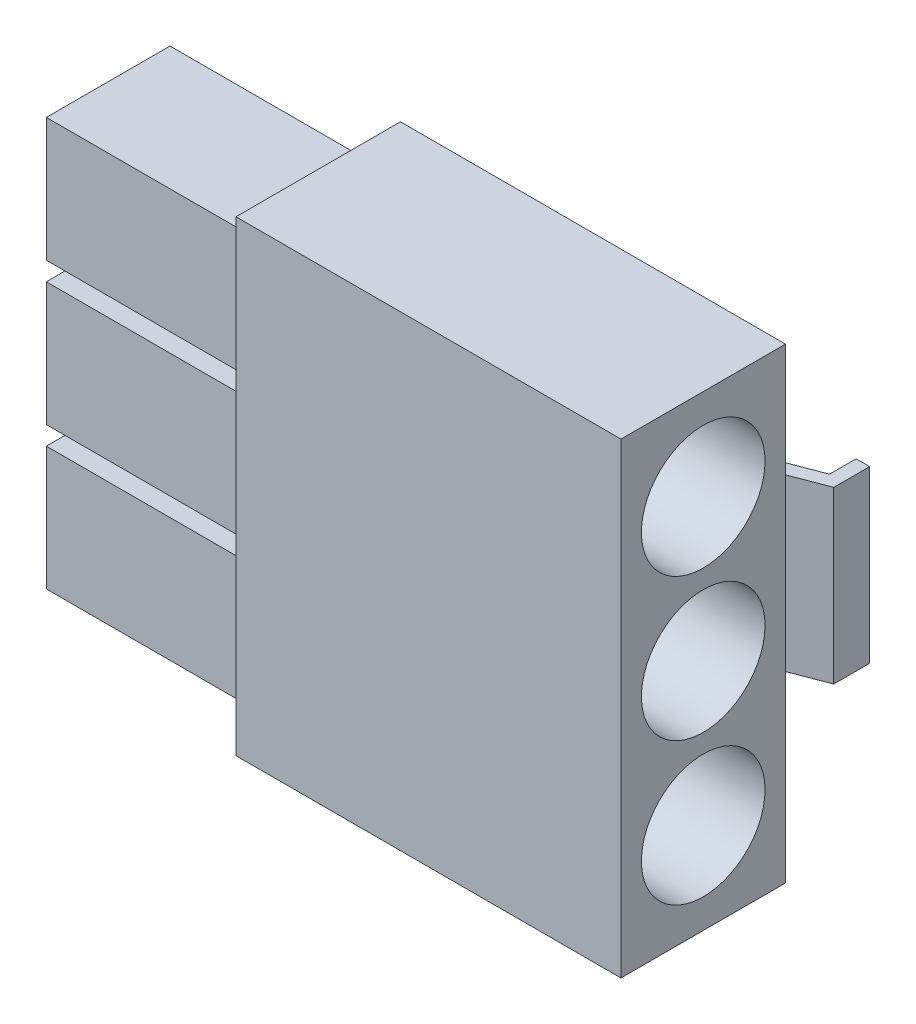
SolidWorks part; units mm, degrees
ref_plane "前视基准面" through (0, 0, 0) normal (0, 0, 1) x (1, 0, 0)
ref_plane "上视基准面" through (0, 0, 0) normal (0, 1, 0) x (1, 0, 0)
ref_plane "右视基准面" through (0, 0, 0) normal (1, 0, 0) x (0, 0, -1)
sketch "草图1" plane through (0, 0, 0) normal (0, 0, 1) x (1, 0, 0)
  line L1 (-8.25, -10) -> (8.25, -10)
  line L2 (-8.25, -10) -> (-8.25, 10)
  line L3 (-8.25, 10) -> (8.25, 10)
  line L4 (8.25, -10) -> (8.25, 10)
  line L5 (-8.25, -10) -> (8.25, 10) construction
  line L6 (-8.25, 10) -> (8.25, -10) construction
  point P0 (0, 0)
  dimension "D1" = 16.5
  dimension "D2" = 20
extrude "凸台-拉伸1" add sketch "草图1" along normal blind 7.05
sketch "草图2" plane through (-8.25, 0, 0) normal (-1, 0, 0) x (0, 0, 1)
  line L0 (0, -10) -> (7.05, 10) construction
  line L1 (0, 10) -> (7.05, -10) construction
  line L2 (0.875, 8.75) -> (6.175, 8.75)
  line L3 (0.875, -2.65) -> (6.175, -2.65)
  line L4 (0.875, -2.65) -> (0.875, 2.65)
  line L5 (0.875, 2.65) -> (6.175, 2.65)
  line L6 (6.175, -2.65) -> (6.175, 2.65)
  line L7 (0.875, -2.65) -> (6.175, 2.65) construction
  line L8 (0.875, 2.65) -> (6.175, -2.65) construction
  line L9 (6.175, 3.45) -> (6.175, 8.75)
  line L10 (0.875, 3.45) -> (6.175, 3.45)
  line L11 (0.875, 3.45) -> (0.875, 8.75)
  line L12 (0.875, -8.75) -> (6.175, -8.75)
  line L13 (0.875, -3.45) -> (6.175, -3.45)
  line L14 (0.875, -8.75) -> (0.875, -3.45)
  line L15 (6.175, -8.75) -> (6.175, -3.45)
  point P8 (3.525, 0)
  dimension "D1" = 5.3
  dimension "D2" = 5.3
  dimension "D3" = 0.8
  dimension "D4" = 0.8
extrude "凸台-拉伸2" add sketch "草图2" along normal blind 9
sketch "草图3" plane through (8.25, 0, 0) normal (1, 0, 0) x (0, 0, -1)
  line L0 (-7.05, -10) -> (0, 10) construction
  line L1 (0, -10) -> (-7.05, 10) construction
  circle A0 centre (-3.525, 0) radius 1.8
  circle A1 centre (-3.525, 6.1) radius 1.8
  circle A2 centre (-3.525, -6.1) radius 1.8
  dimension "D1" = 6.1
  dimension "D2" = 6.1
extrude "切除-拉伸1" cut sketch "草图3" against normal blind 26
sketch "草图4" plane through (8.25, 0, 0) normal (1, 0, 0) x (0, 0, -1)
  circle A0 centre (-3.525, 0) radius 2.65
  circle A1 centre (-3.525, 6.1) radius 2.65
  circle A2 centre (-3.525, -6.1) radius 2.65
extrude "切除-拉伸4" cut sketch "草图4" against normal blind 16
sketch "草图6" plane through (0, 0, 0) normal (0, 1, 0) x (1, 0, 0)
  line L0 (-3.2059, 0.8347) -> (5.0205, 0.8347)
  line L1 (5.0205, 0.8347) -> (8.25, 2.0671)
  line L2 (8.25, 2.0671) -> (8.25, 3.6077)
  line L3 (8.25, 3.6077) -> (7.67, 3.6077)
  line L4 (-3.2059, 1.4147) -> (4.9136, 1.4147)
  line L5 (4.9136, 1.4147) -> (7.67, 2.4666)
  line L6 (7.67, 2.4666) -> (7.67, 3.0277)
  line L7 (7.67, 3.0277) -> (7.67, 3.6077)
  line L9 (-3.2059, 0) -> (-4.007, 0)
  line L10 (8.25, 0) -> (-8.25, 0) construction
  line L11 (-4.007, 0) -> (-4.007, 1.4147)
  line L12 (-4.007, 1.4147) -> (-3.2059, 1.4147)
  line L13 (-3.2059, 0.8347) -> (-3.2059, 0)
  line L14 (8.25, 3.6077) -> (7.4546, 3.6077) construction
  line L15 (7.67, 3.0277) -> (7.4546, 3.0277) construction
  dimension "D1" = 0.58
extrude "凸台-拉伸3" add sketch "草图6" along normal blind 3.65 and the other way blind 3.65
sketch "草图7" plane through (0, 0, 0) normal (0, 1, 0) x (1, 0, 0)
  line L0 (6.2918, 1.9407) -> (-11.2894, 1.9407)
  line L1 (7.67, 2.4666) -> (4.9136, 1.4147) construction
  line L2 (-11.2894, 1.9407) -> (-11.2894, 1.0313)
  line L3 (-11.2894, 1.0313) -> (-10.5417, -0.0376)
  line L4 (-10.5417, -0.0376) -> (-10.5417, 1.0313)
  line L5 (-10.5417, 1.0313) -> (-4.007, 1.0313)
  line L6 (-4.007, 1.4147) -> (-4.007, 0) construction
  line L7 (-4.007, 1.0313) -> (-4.007, 1.4147)
  line L8 (-4.007, 1.4147) -> (4.9136, 1.4147)
  line L9 (4.9136, 1.4147) -> (6.2918, 1.9407)
extrude "凸台-拉伸4" add sketch "草图7" along normal blind 1.5 and the other way blind 1.5
sketch "草图8" plane through (8.25, 0, 0) normal (1, 0, 0) x (0, 0, -1)
  point P0 (-3.525, -6.1)
  point P1 (-3.525, 0)
  point P3 (-3.525, 6.1)
sketch "0_0_Point" plane through (8.25, 0, 0) normal (1, 0, 0) x (0, 0, -1)
  point P0 (-3.525, -6.1)
other "0_0" parameters "直径"=2, "端头长度"=2
ref_axis "基准轴1" through (18.25, -6.1, 3.525) along (-1, 0, 0)
sketch "1_0_Point" plane through (8.25, 0, 0) normal (1, 0, 0) x (0, 0, -1)
  point P0 (-3.525, 0)
other "1_0" parameters "直径"=2, "端头长度"=2
ref_axis "基准轴2" through (18.25, 0, 3.525) along (-1, 0, 0)
sketch "2_0_Point" plane through (8.25, 0, 0) normal (1, 0, 0) x (0, 0, -1)
  point P0 (-3.525, 6.1)
other "2_0" parameters "直径"=2, "端头长度"=2
ref_axis "基准轴3" through (18.25, 6.1, 3.525) along (-1, 0, 0)
